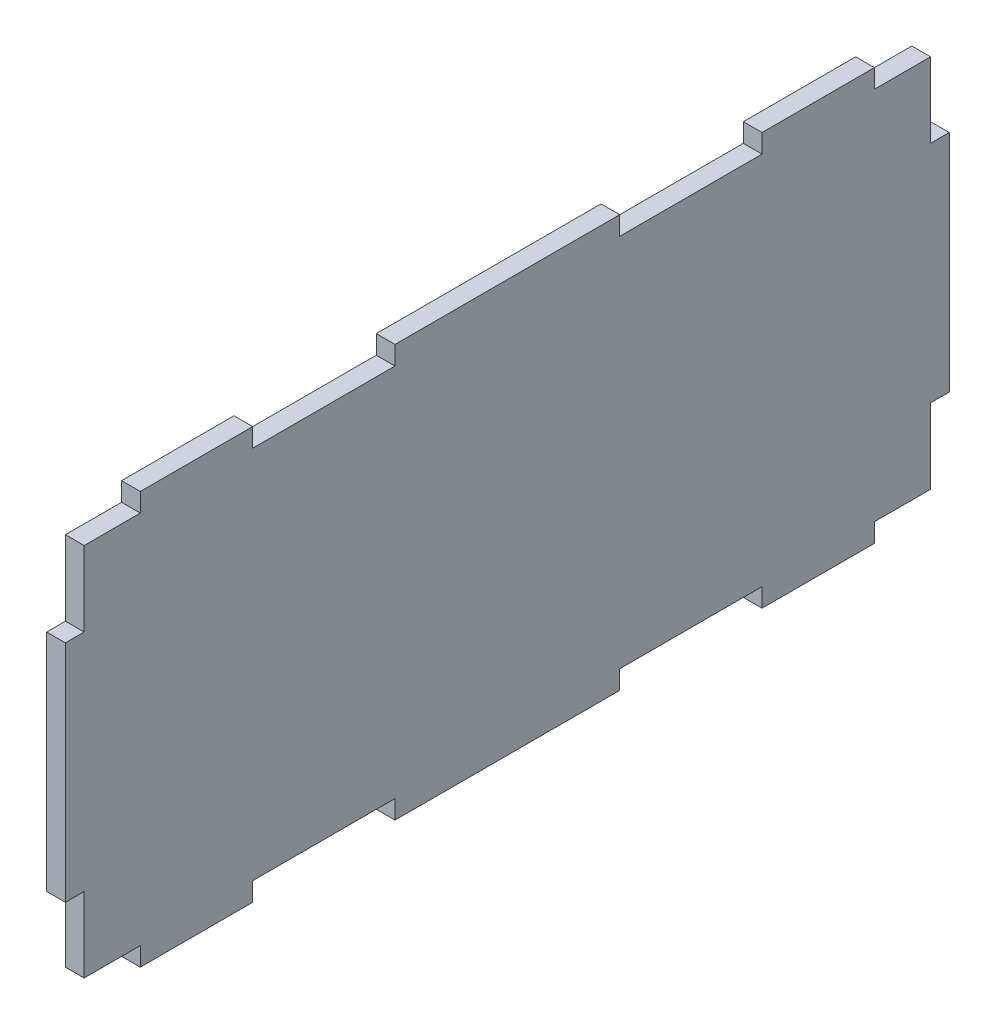
SolidWorks part; units mm, degrees
ref_plane "Front Plane" through (0, 0, 0) normal (0, 0, 1) x (1, 0, 0)
ref_plane "Top Plane" through (0, 0, 0) normal (0, 1, 0) x (1, 0, 0)
ref_plane "Right Plane" through (0, 0, 0) normal (1, 0, 0) x (0, 0, -1)
sketch "Sketch1" plane through (0, 0, 0) normal (1, 0, 0) x (0, 0, -1)
  line L0 (-113, 0) -> (113, 0) construction
  line L1 (113, -50) -> (-113, -50)
  line L2 (113, -50) -> (113, 50)
  line L3 (113, 50) -> (-113, 50)
  line L4 (-113, -50) -> (-113, 50)
  line L5 (113, -50) -> (-113, 50) construction
  line L6 (113, 50) -> (-113, -50) construction
  line L7 (0, -50) -> (0, 50) construction
  line L8 (113, -30) -> (118, -30)
  line L9 (98, 50) -> (68, 50)
  line L10 (98, 50) -> (98, 55)
  line L11 (98, 55) -> (68, 55)
  line L12 (68, 50) -> (68, 55)
  line L13 (0, 50) -> (30, 50)
  line L14 (0, 50) -> (0, 55)
  line L15 (-30, 55) -> (30, 55)
  line L16 (30, 50) -> (30, 55)
  line L17 (113, 0) -> (118, 0)
  line L18 (113, 0) -> (113, 30)
  line L19 (113, 30) -> (118, 30)
  line L20 (118, -30) -> (118, 30)
  line L21 (98, -50) -> (98, -55)
  line L22 (68, -50) -> (68, -55)
  line L23 (98, -55) -> (68, -55)
  line L24 (30, -50) -> (30, -55)
  line L25 (-30, -55) -> (30, -55)
  line L26 (-30, -50) -> (-30, -55)
  line L27 (-68, -50) -> (-68, -55)
  line L28 (-98, -50) -> (-98, -55)
  line L29 (-98, -55) -> (-68, -55)
  line L30 (-113, -30) -> (-118, -30)
  line L31 (-118, -30) -> (-118, 30)
  line L32 (-113, 30) -> (-118, 30)
  line L33 (-98, 50) -> (-98, 55)
  line L34 (-68, 50) -> (-68, 55)
  line L35 (-98, 55) -> (-68, 55)
  line L36 (-30, 50) -> (-30, 55)
  line L37 (30, 50) -> (-30, 50)
  line L38 (-68, 50) -> (-98, 50)
  line L39 (-113, 30) -> (-113, -30)
  line L40 (-98, -50) -> (-68, -50)
  line L41 (-30, -50) -> (30, -50)
  line L42 (68, -50) -> (98, -50)
  line L43 (113, -30) -> (113, 30)
  line L44 (98, 50) -> (68, 50)
  point P0 (0, 0)
  point P17 (98, 52.5)
  point P32 (0, -55)
  dimension "D1" = 226
  dimension "D2" = 100
  dimension "D3" = 5
  dimension "D4" = 5
  dimension "D5" = 15
  dimension "D6" = 30
  dimension "D7" = 30
  dimension "D8" = 5
  dimension "D9" = 30
extrude "Boss-Extrude1" add sketch "Sketch1" along normal blind 5 contours L4 L1 L2 L3 | L35 L33 L3 L34 | L28 L29 L27 L1 | L4 L32 L31 L30 | L12 L3 L10 L11 | L37 L36 L15 L16 | L25 L24 L41 L26 | L23 L22 L42 L21 | L43 L8 L20 L19 region at (0, 0, 0) region at (0, -52.5, 83) region at (0, 52.5, -83) region at (0, 0, 115.5) region at (0, 52.5, 83)
